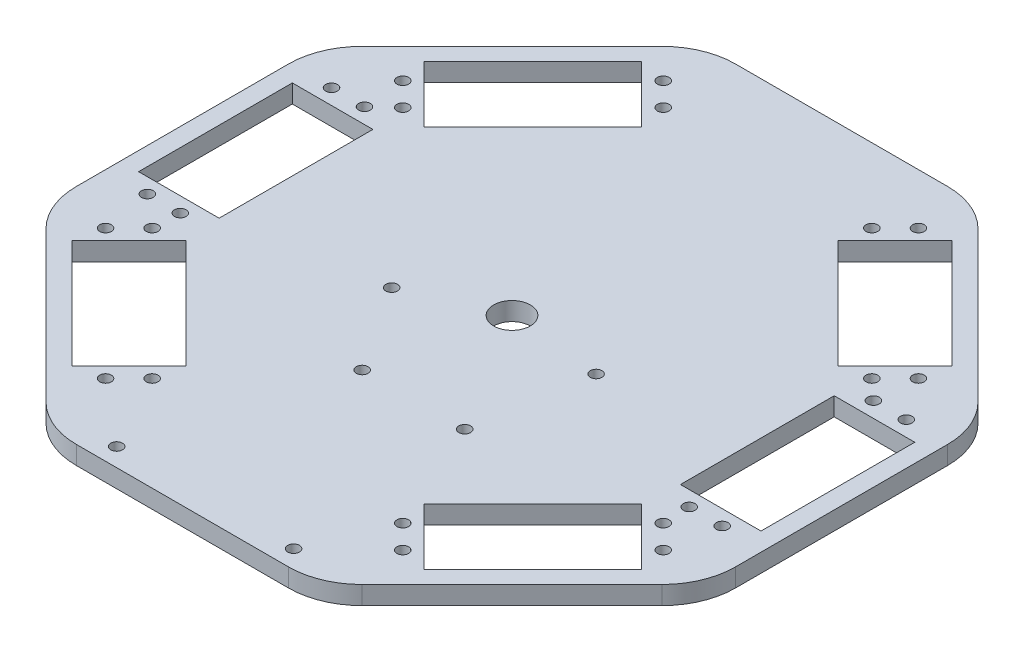
SolidWorks part; units mm, degrees
ref_plane "Front Plane" through (0, 0, 0) normal (0, 0, 1) x (1, 0, 0)
ref_plane "Top Plane" through (0, 0, 0) normal (0, 1, 0) x (1, 0, 0)
ref_plane "Right Plane" through (0, 0, 0) normal (1, 0, 0) x (0, 0, -1)
sketch "Sketch1" plane through (0, 0, 0) normal (0, 1, 0) x (1, 0, 0)
  line L1 (-90, -37.2792) -> (-37.2792, -90)
  line L2 (-37.2792, -90) -> (37.2792, -90)
  line L3 (37.2792, -90) -> (90, -37.2792)
  line L4 (90, -37.2792) -> (90, 37.2792)
  line L5 (90, 37.2792) -> (37.2792, 90)
  line L6 (37.2792, 90) -> (-37.2792, 90)
  line L7 (-37.2792, 90) -> (-90, 37.2792)
  line L8 (-90, 37.2792) -> (-90, -37.2792)
  line L12 (63.6396, -63.6396) -> (0, 0) construction
  line L21 (-20.4, -34.5422) -> (-34.5422, -20.4)
  line L22 (-20.4, -34.5422) -> (-50.0985, -64.2407)
  line L23 (-50.0985, -64.2407) -> (-64.2407, -50.0985)
  line L24 (-34.5422, -20.4) -> (-64.2407, -50.0985)
  line L25 (-38.85, -10) -> (-38.85, 10)
  line L26 (-38.85, -10) -> (-80.85, -10)
  line L27 (-80.85, -10) -> (-80.85, 10)
  line L28 (-38.85, 10) -> (-80.85, 10)
  line L29 (-34.5422, 20.4) -> (-20.4, 34.5422)
  line L30 (-34.5422, 20.4) -> (-64.2407, 50.0985)
  line L31 (-64.2407, 50.0985) -> (-50.0985, 64.2407)
  line L32 (-20.4, 34.5422) -> (-50.0985, 64.2407)
  line L37 (20.4, 34.5422) -> (34.5422, 20.4)
  line L38 (20.4, 34.5422) -> (50.0985, 64.2407)
  line L39 (50.0985, 64.2407) -> (64.2407, 50.0985)
  line L40 (34.5422, 20.4) -> (64.2407, 50.0985)
  line L41 (38.85, 10) -> (38.85, -10)
  line L42 (38.85, 10) -> (80.85, 10)
  line L43 (80.85, 10) -> (80.85, -10)
  line L44 (38.85, -10) -> (80.85, -10)
  circle A0 centre (0, 0) radius 90 construction
  circle A13 centre (0, 0) radius 90 construction
  circle A14 centre (-27.7186, -21.3546) radius 2.5
  circle A15 centre (-21.3546, -27.7186) radius 2.5
  circle A16 centre (-56.9221, -63.2861) radius 2.5
  circle A17 centre (-63.2861, -56.9221) radius 2.5
  circle A18 centre (0, 0) radius 90 construction
  circle A19 centre (-34.7, 4.5) radius 2.5
  circle A20 centre (-34.7, -4.5) radius 2.5
  circle A21 centre (-85, -4.5) radius 2.5
  circle A22 centre (-85, 4.5) radius 2.5
  circle A23 centre (0, 0) radius 90 construction
  circle A24 centre (-21.3546, 27.7186) radius 2.5
  circle A25 centre (-27.7186, 21.3546) radius 2.5
  circle A26 centre (-63.2861, 56.9221) radius 2.5
  circle A27 centre (-56.9221, 63.2861) radius 2.5
  circle A28 centre (0, 0) radius 90 construction
  circle A33 centre (0, 0) radius 90 construction
  circle A34 centre (27.7186, 21.3546) radius 2.5
  circle A35 centre (21.3546, 27.7186) radius 2.5
  circle A36 centre (56.9221, 63.2861) radius 2.5
  circle A37 centre (63.2861, 56.9221) radius 2.5
  circle A38 centre (0, 0) radius 90 construction
  circle A39 centre (34.7, -4.5) radius 2.5
  circle A40 centre (34.7, 4.5) radius 2.5
  circle A41 centre (85, 4.5) radius 2.5
  circle A42 centre (85, -4.5) radius 2.5
  circle A43 centre (0, 0) radius 90 construction
  point P15 (63.6396, -63.6396)
  point P16 (60.1041, -60.1041)
  point P17 (57.1696, -57.1696)
  point P121 (0, 0)
  dimension "D1" = 90
  dimension "D12" = 8
extrude "Baseplate" add sketch "Sketch1" along normal blind 5 contours L7 L8 L1 L2 L3 L4 L5 L6 A42 A41 A40 A39 A37 A36 A35 A34 A27 A26 A25 A24 A22 A21 A20 A19 A17 A16 A15 A14 L44 L41 | L29 L32 L31 L30 | L37 L40 L39 L38 | L41 L44 L43 L42 | L25 L28 L27 L26 | A27 | A26 | A25 | A24 | A22 | A21 | A19 | A20 | A14 | A15 | A17 | A16 | A40 | A41 | A42 | A35 | A34 | A39 | A37 | A36 | L21 L24 L23 L22 region at (1.7472, 0, 1.7472) region at (-59.85, 0, 0) region at (-42.3203, 0, -42.3203) region at (42.3203, 0, -42.3203) region at (59.85, 0, 0) region at (-27.7186, 0, 21.3546) region at (-21.3546, 0, 27.7186) region at (-56.9221, 0, 63.2861) region at (-63.2861, 0, 56.9221) region at (-34.7, 0, -4.5) region at (-34.7, 0, 4.5) region at (-85, 0, 4.5) region at (-85, 0, -4.5) region at (-21.3546, 0, -27.7186) region at (-27.7186, 0, -21.3546) region at (-63.2861, 0, -56.9221) region at (-56.9221, 0, -63.2861) region at (34.7, 0, -4.5) region at (85, 0, -4.5) region at (85, 0, 4.5)
fillet "Fillet1" radius 20 8 edges at (-90, 2.5, -37.2792) (-37.2792, 2.5, -90) (37.2792, 2.5, -90) (90, 2.5, -37.2792) (90, 2.5, 37.2792) (37.2792, 2.5, 90) (-37.2792, 2.5, 90) (-90, 2.5, 37.2792)
sketch "Sketch2" plane through (0, 5, 0) normal (0, 1, 0) x (1, 0, 0)
  line L0 (90, -28.9949) -> (90, 28.9949) construction
  line L1 (63, 25.0051) -> (85, 25.0051)
  line L2 (63, 25.0051) -> (63, -16.9949)
  line L3 (63, -16.9949) -> (85, -16.9949)
  line L4 (85, 25.0051) -> (85, -16.9949)
  circle A0 centre (78.5, 29.2051) radius 1.6
  circle A1 centre (69.5, 29.2051) radius 1.6
  circle A2 centre (69.5, -21.0949) radius 1.6
  circle A3 centre (78.5, -21.0949) radius 1.6
  point P8 (74, 25.0051)
  dimension "D1" = 3.2
  dimension "D2" = 9
  dimension "D3" = 50.3
  dimension "D4" = 22
  dimension "D5" = 42
  dimension "D6" = 4.2
  dimension "D7" = 4.5
  dimension "D8" = 5
  dimension "D9" = 12
extrude "Servo hole" cut sketch "Sketch2" against normal through all contours A0 | L4 L1 L2 L3 | A2 | A3 | A1 region at (74, 5, -4.0051) region at (78.5, 5, -29.2051) region at (69.5, 5, 21.0949) region at (78.5, 5, 21.0949)
sketch "Sketch3" plane through (0, 5, 0) normal (0, 1, 0) x (1, 0, 0)
  circle A0 centre (0, 0) radius 5
  dimension "D1" = 10
extrude "Center hole" cut sketch "Sketch3" against normal through all
pattern_circular "Servo hole pattern" count 8 over 360 about axis through (0, 5, 0) along (0, 1, 0) skipping 2, 3, 4, 5, 6 of "Servo hole"
sketch "Sketch4" plane through (0, 5, 0) normal (0, 1, 0) x (1, 0, 0)
  line L0 (-28.9949, -90) -> (28.9949, -90) construction
  line L1 (-90, 28.9949) -> (-90, -28.9949) construction
  circle A0 centre (-23, -9.8668) radius 1.6
  circle A1 centre (-23, -85) radius 1.6
  circle A2 centre (25.3362, -2.3738) radius 1.6
  circle A3 centre (25.3362, -85) radius 1.6
  circle A4 centre (-7.5585, -33.3745) radius 1.6
  circle A5 centre (20.4577, -33.3745) radius 1.6
  point P12 (0, 0)
  point P13 (0, 0)
  point P14 (0, 0)
  point P15 (0, 0)
  point P16 (-7.8431, -12.1787)
  point P17 (0, 0)
  point P18 (-23.2441, 11.8323)
  point P19 (0, 0)
  point P20 (-8.84, -10.6562)
  point P23 (0, 0)
  dimension "D1" = 3.2
  dimension "D8" = 5
  dimension "D2" = 7.493
  dimension "D3" = 48.3362
  dimension "D4" = 31.0007
  dimension "D5" = 51.6255
  dimension "D6" = 4.8785
  dimension "D7" = 28.0162
  dimension "D9" = 67
extrude "Arduino Screw holes" cut sketch "Sketch4" against normal through all
ref_plane "Midplane" through (0, 0, 0) normal (1, 0, 0) x (0, 0, -1)
mirror "Mirror1" about plane through (0, 0, 0) normal (1, 0, 0) of "Servo hole pattern", "Servo hole"
